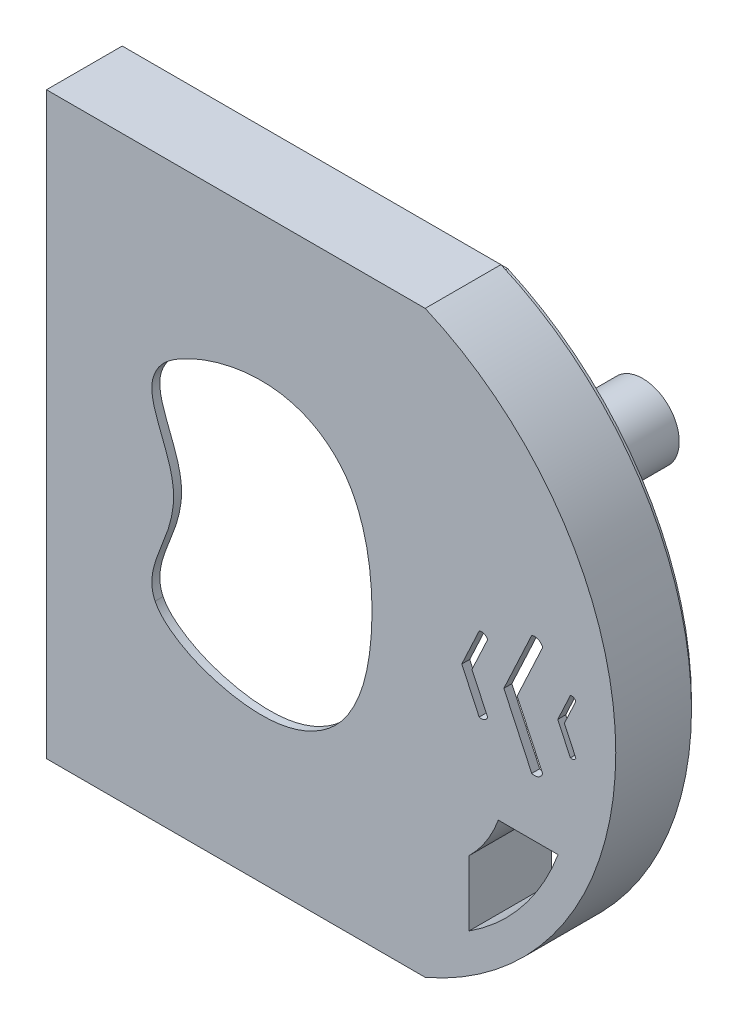
SolidWorks part; units mm, degrees
ref_plane "Front Plane" through (0, 0, 0) normal (0, 0, 1) x (1, 0, 0)
ref_plane "Top Plane" through (0, 0, 0) normal (0, 1, 0) x (1, 0, 0)
ref_plane "Right Plane" through (0, 0, 0) normal (1, 0, 0) x (0, 0, -1)
sketch "Sketch1" plane through (0, 0, 0) normal (0, 0, 1) x (1, 0, 0)
  line L1 (-74.2297, 45.7275) -> (-49.2297, 45.7275)
  line L2 (-74.2297, 45.7275) -> (-74.2297, 5.7275)
  line L3 (-74.2297, 5.7275) -> (-49.2297, 5.7275)
  line L4 (-49.2297, 45.7275) -> (-49.2297, 5.7275)
  dimension "D1" = 40
  dimension "D2" = 25
extrude "Boss-Extrude1" add sketch "Sketch1" along normal blind 0.5 and the other way blind 0.0001
sketch "Sketch2" plane through (0, 0, 0) normal (0, 0, 1) x (1, 0, 0)
  line L0 (-77.8888, 47.5275) -> (-77.8888, 3.9275)
  line L5 (-61.7297, 45.7275) -> (-61.7297, 25.7275)
  line L6 (-49.2297, 45.7275) -> (-74.2297, 45.7275) construction
  line L8 (-77.8888, 47.5275) -> (-49.3888, 47.5275)
  line L10 (-77.8888, 3.9275) -> (-49.3888, 3.9275)
  circle A1 centre (-42.3892, 25.7624) radius 48.5612
  arc A3 (-49.3888, 47.5275) -> (-49.3888, 3.9275) centre (-58.7867, 25.7275) cw
  dimension "D6" = 43.6
  dimension "D8" = 28.5
  dimension "D9" = 28.5
extrude "Boss-Extrude5" add sketch "Sketch2" along normal blind 6.1 and the other way blind 0.1 contours L8 L0 region at (-58.2685, 25.7275, 0)
sketch "Sketch8" plane through (0, 0, 0) normal (0, 0, 1) x (1, 0, 0)
  line L0 (-76.8888, 46.5275) -> (-76.8888, 4.9275)
  line L1 (-76.8888, 4.9275) -> (-49.3888, 4.9275)
  line L2 (-76.8888, 46.5275) -> (-49.3888, 46.5275)
  line L3 (-77.8888, 47.5275) -> (-77.8888, 3.9275) construction
  arc A0 (-49.3888, 4.9275) -> (-49.3888, 46.5275) centre (-58.9321, 25.7275) ccw
  arc A2 (-49.3888, 3.9275) -> (-49.3888, 47.5275) centre (-58.7867, 25.7275) ccw construction
  point P8 (-36.0473, 25.7275)
  point P12 (-35.0473, 25.7275)
  dimension "D1" = 1
  dimension "D2" = 1
  dimension "D3" = 1
  dimension "D4" = 1
extrude "Cut-Extrude2" cut sketch "Sketch8" against normal blind 4 and the other way blind 5.5 contours A0 L2 L0 L1
sketch "Sketch9" plane through (0, 0, 0) normal (0, 0, 1) x (1, 0, 0)
  line L0 (-37.7093, 30.2625) -> (-37.7093, 29.3916)
  line L1 (-37.7093, 22.0742) -> (-37.7093, 21.228)
  line L2 (-46.6022, 30.9745) -> (-46.6022, 30.0766)
  line L3 (-46.6022, 21.3784) -> (-46.6022, 20.6468)
  arc A3 (-37.7093, 30.2625) -> (-46.6022, 30.9745) centre (-42.5385, 25.8379) ccw
  arc A4 (-37.7093, 21.228) -> (-46.6022, 20.6468) centre (-42.4688, 25.7275) cw
  arc A5 (-37.7093, 29.3916) -> (-46.6022, 30.0766) centre (-42.4641, 25.732) ccw
  arc A6 (-37.7093, 22.0742) -> (-46.6022, 21.3784) centre (-42.4688, 25.7275) cw
sketch "Sketch11" plane through (0, 0, -0.1) normal (0, 0, -1) x (-1, 0, 0)
  line L0 (76.8888, 46.5275) -> (76.8888, 4.9275) construction
  line L1 (49.3888, 47.5275) -> (77.8888, 47.5275)
  line L2 (49.3888, 4.4275) -> (77.3888, 4.4275)
  line L3 (77.3888, 4.4275) -> (77.3888, 47.0275)
  line L4 (77.3888, 47.0275) -> (49.3888, 47.0275)
  line L5 (77.8888, 47.5275) -> (77.8888, 3.9275)
  line L6 (77.8888, 3.9275) -> (49.3888, 3.9275)
  arc A0 (49.3888, 47.0275) -> (49.3888, 4.4275) centre (58.8568, 25.7275) ccw
  arc A1 (49.3888, 47.5275) -> (49.3888, 3.9275) centre (58.7867, 25.7275) ccw construction
  arc A2 (49.3888, 47.5275) -> (49.3888, 3.9275) centre (58.7867, 25.7275) ccw
  point P16 (35.0473, 25.7275)
  point P17 (35.5473, 25.7275)
  dimension "D1" = 0.5
  dimension "D2" = 0.5
  dimension "D3" = 0.5
  dimension "D4" = 0.5
extrude "Cut-Extrude3" cut sketch "Sketch11" against normal blind 0.5
sketch "Sketch16" plane through (-77.8888, 0, 0) normal (-1, 0, 0) x (0, 0, 1)
  line L0 (3.4, 25.7275) -> (3.4, 28.7275)
  line L4 (3.4, 25.7275) -> (3.4, 22.7275)
  line L6 (-2.6, 25.7275) -> (3.4, 28.7275)
  line L8 (-2.6, 25.7275) -> (3.4, 22.7275)
extrude "Cut-Extrude4" cut sketch "Sketch16" against normal blind 0.4 contours L8 L4 L0 L6
sketch "Sketch21" plane through (0, 0, 0) normal (0, 0, 1) x (1, 0, 0)
  line L8 (-46.6022, 13.7463) -> (-46.6022, 7.8405)
  line L12 (-39.3888, 16.9275) -> (-43.8888, 16.9275)
  line L29 (-46.1022, 8.5905) -> (-46.1022, 13.4963)
  line L30 (-39.3888, 17.4104) -> (-38.8722, 17.4104)
  line L34 (-43.8888, 17.4104) -> (-44.4053, 17.4104)
  line L39 (-46.6022, 13.4963) -> (-46.6022, 13.7463)
  line L43 (-46.6022, 8.5905) -> (-46.6022, 7.8405)
  line L44 (-44.4053, 17.4104) -> (-38.8722, 17.4104)
  arc A0 (-43.8888, 16.9275) -> (-46.1022, 13.4963) centre (-52.5399, 20.0787) cw
  arc A1 (-39.3888, 16.9275) -> (-46.1022, 8.5905) centre (-55.3129, 22.8791) cw
  arc A5 (-44.4053, 17.4104) -> (-46.6022, 13.7463) centre (-53.185, 20.1837) cw
  arc A6 (-38.8722, 17.4104) -> (-46.6022, 7.8405) centre (-55.0658, 22.5839) cw
  dimension "D1" = 4.9057
  dimension "D4" = 0.559
  dimension "D7" = 5.9057
sketch "Sketch26" plane through (0, 0, 5.5) normal (0, 0, -1) x (-1, 0, 0)
  line L0 (49.3888, 46.5275) -> (49.3888, 37.5275)
  circle A0 centre (43.8888, 37.5275) radius 1.25
  circle A1 centre (43.8888, 37.5275) radius 2.75
  point P6 (40.8845, 39.6012)
  dimension "D1" = 2.5
  dimension "D2" = 5.5
extrude "Boss-Extrude10" add sketch "Sketch26" along normal blind 10.2672 contours A1 A0 | A1 | A0 region at (-41.2165, 37.5275, 5.5)
extrude "Cut-Extrude10" cut sketch "Sketch21" against normal blind 8.134 and the other way blind 12 contours L12 A0 L29 A1
sketch "Sketch31" plane through (0, 0, 0) normal (0, 0, 1) x (1, 0, 0)
  line L8 (-46.6022, 13.7463) -> (-46.6022, 7.8405)
  line L44 (-44.4053, 17.4104) -> (-38.8722, 17.4104)
  line L45 (-46.1022, 8.5905) -> (-46.1022, 13.4963)
  line L46 (-39.3888, 16.9275) -> (-43.8888, 16.9275)
  arc A5 (-44.4053, 17.4104) -> (-46.6022, 13.7463) centre (-53.185, 20.1837) cw
  arc A6 (-38.8722, 17.4104) -> (-46.6022, 7.8405) centre (-55.0658, 22.5839) cw
  arc A7 (-46.1022, 8.5905) -> (-39.3888, 16.9275) centre (-55.3129, 22.8791) ccw
  arc A8 (-43.8888, 16.9275) -> (-46.1022, 13.4963) centre (-52.5399, 20.0787) cw
  dimension "D7" = 5.9057
extrude "Boss-Extrude11" add sketch "Sketch31" along normal blind 6.099 and the other way blind 0.1
sketch "Sketch32" plane through (0, 0, 6.1) normal (0, 0, 1) x (1, 0, 0)
  line L0 (-49.3888, 47.5275) -> (-49.3888, 3.9275)
  line L12 (-64.7084, -25.1636) -> (-66.7039, -20.6501)
  line L14 (-64.7084, -25.1636) -> (-66.8882, -29.8381)
  line L25 (-41.371, 30.2264) -> (-43.4688, 25.7275)
  line L28 (-41.371, 21.2287) -> (-43.4688, 25.7275)
  line L32 (-45.3278, 28.5317) -> (-46.6354, 25.7275)
  line L33 (-46.6354, 25.7275) -> (-45.3278, 22.9234)
  line L35 (-39.4125, 25.7275) -> (-38.464, 23.6935)
  line L40 (-39.4125, 25.7275) -> (-38.464, 27.7616)
  line L44 (-44.6869, 28.2943) -> (-45.8695, 25.7583)
  line L45 (-45.8695, 25.7583) -> (-44.6869, 23.2222)
  line L46 (-38.0533, 27.57) -> (-38.9125, 25.7275)
  line L47 (-38.9125, 25.7275) -> (-38.0533, 23.885)
  line L48 (-40.5496, 21.6117) -> (-42.4688, 25.7275)
  line L49 (-42.4688, 25.7275) -> (-40.5496, 29.8433)
  arc A0 (-44.6869, 23.2222) -> (-45.3278, 22.9234) centre (-45.1568, 23.3933) cw
  arc A2 (-44.6869, 28.2943) -> (-45.3278, 28.5317) centre (-45.1341, 28.0707) ccw
  arc A4 (-38.0533, 23.885) -> (-38.464, 23.6935) centre (-38.3544, 23.9946) cw
  arc A5 (-40.5496, 21.6117) -> (-41.371, 21.2287) centre (-41.1518, 21.8309) cw
  arc A6 (-41.371, 30.2264) -> (-40.5496, 29.8433) centre (-41.1518, 29.6242) cw
  arc A7 (-38.0533, 27.57) -> (-38.464, 27.7616) centre (-38.3544, 27.4604) ccw
extrude "Cut-Extrude11" cut sketch "Sketch32" against normal blind 6.134 contours L40 L35 | L28 L25 | L33 L32 region at (-40.9212, 30.1186, 6.1) region at (-44.9813, 28.4832, 6.1) region at (-38.899, 26.7263, 6.1)
sketch "Sketch33" plane through (0, 0, 0) normal (0, 0, 1) x (1, 0, 0)
  line L0 (-35.0473, 25.7275) -> (-77.8888, 25.7275)
  line L1 (-77.8888, 47.5275) -> (-77.8888, 3.9275) construction
  arc A0 (-49.3888, 3.9275) -> (-49.3888, 47.5275) centre (-58.7867, 25.7275) ccw construction
  spline S0 degree 3 poles (-69.7155, 18.2832) (-70.0608, 19.0122) (-69.8938, 20.7821) (-68.885, 22.8038) (-68.4119, 24.5765) (-68.2539, 26.022) (-68.5483, 27.644) (-69.1844, 29.246) (-69.7845, 30.7924) (-70.1192, 32.2842) (-69.3838, 34.0683) (-67.3795, 35.3657) (-64.6417, 36.4038) (-61.448, 36.8282) (-58.0624, 36.164) (-55.4514, 34.1332) (-53.6917, 30.4586) (-53.4083, 27.6398) (-53.384, 25.7513) knots 0 0 0 0 0.056113 0.130583 0.168191 0.193562 0.239298 0.290151 0.322884 0.364734 0.400905 0.460049 0.537277 0.621513 0.698396 0.791261 0.857327 1 1 1 1
  spline S1 degree 3 poles (-53.384, 25.7513) (-53.4198, 23.7713) (-53.7116, 20.6353) (-55.8525, 16.8571) (-59.6416, 14.5638) (-64.3205, 14.8709) (-67.9897, 16.3754) (-69.4248, 17.6944) (-69.7155, 18.2832) knots 0 0 0 0 0.24488 0.378469 0.518271 0.765302 0.920676 1 1 1 1
extrude "Cut-Extrude15" cut sketch "Sketch33" against normal blind 1.134 and the other way blind 45 contours S0 S1
sketch "Sketch39" plane through (-77.8888, 0, 0) normal (-1, 0, 0) x (0, 0, 1)
  line L3 (4.25, 36.8775) -> (4.25, 35.8775)
  line L5 (4.25, 35.8775) -> (2.25, 35.8775)
  line L6 (4.25, 35.8775) -> (4.25, 37.8775)
  line L7 (4.25, 37.8775) -> (2.25, 37.8775)
  line L8 (2.25, 35.8775) -> (2.25, 37.8775)
extrude "Boss-Extrude13" add sketch "Sketch39" along normal blind 0.0001 and the other way blind 3 contours L8 L5 L3 L6 L7 region at (-77.8888, 36.8775, 3.25)
sketch "Sketch40" plane through (-77.8889, 0, 0) normal (-1, 0, 0) x (0, 0, 1)
  line L1 (2.25, 37.8775) -> (4.25, 37.8775)
  line L2 (2.25, 37.8775) -> (2.25, 35.8775)
  line L3 (2.25, 35.8775) -> (4.25, 35.8775)
  line L4 (4.25, 37.8775) -> (4.25, 35.8775)
extrude "Cut-Extrude17" cut sketch "Sketch40" against normal blind 0.25
sketch "Sketch41" plane through (-77.8888, 0, 0) normal (-1, 0, 0) x (0, 0, 1)
  point P4 (-1.5055, 39.5439)
sketch "Sketch43" plane through (-77.8888, 0, 0) normal (-1, 0, 0) x (0, 0, 1)
  circle A0 centre (3.25, 36.8775) radius 0.25
extrude "Cut-Extrude19" cut sketch "Sketch43" against normal blind 3.25 contours A0
sketch "Sketch45" plane through (0, 0, 2.25) normal (0, 0, -1) x (-1, 0, 0)
  line L5 (74.8888, 37.8775) -> (76.8888, 37.8775) construction
  line L6 (76.8888, 35.8775) -> (75.8888, 35.8775)
  line L7 (76.8888, 35.8775) -> (76.8888, 37.8775)
  line L8 (76.8888, 37.8775) -> (75.8888, 37.8775)
  line L9 (75.8888, 35.8775) -> (75.8888, 37.8775)
extrude "Boss-Extrude14" add sketch "Sketch45" along normal blind 6.25
sketch "Sketch51" plane through (0, 37.8775, 0) normal (0, 1, 0) x (1, 0, 0)
  line L0 (-75.8888, 4) -> (-76.8888, 2.05)
  line L1 (-76.8888, 4) -> (-76.8888, 0.1) construction
  line L2 (-76.8888, 2.05) -> (-75.4934, 2.05)
  line L3 (-75.4934, 2.05) -> (-75.8888, 4)
  line L4 (-76.8888, 2.05) -> (-76.8888, 4)
  line L5 (-76.8888, 4) -> (-75.8888, 4)
  line M3 (-75.8888, 4) -> (-76.8888, 4)
  line M4 (-76.8888, 4) -> (-76.8888, 0.1)
extrude "Cut-Extrude21" cut sketch "Sketch51" against normal blind 4.25 and the other way blind 2 contours L0 M3 M4 region at (-76.5554, 37.8775, -3.35)
sketch "Sketch52" plane through (0, 37.8775, 0) normal (0, 1, 0) x (1, 0, 0)
  line L0 (-75.6888, 2.05) -> (-75.4888, 2.05)
  line L1 (-75.8888, 4) -> (-75.4888, 2.05)
  line L3 (-75.8888, 4) -> (-75.8888, -2.25) construction
  line L4 (-75.8888, 3.025) -> (-75.6888, 2.05)
  line L11 (-75.8888, 4) -> (-76.8888, 2.05)
  line L12 (-76.8888, 2.05) -> (-76.8888, 0.1)
  line L13 (-76.8888, 0.1) -> (-76.8888, -4.25)
  line L14 (-76.8888, -4.25) -> (-74.8888, -4.25)
  line L15 (-74.8888, -4.25) -> (-74.8888, -2.25)
  line L16 (-74.8888, -2.25) -> (-75.8888, -2.25)
  line L17 (-75.8888, -2.25) -> (-75.8888, 4)
  line L18 (-75.8888, 4) -> (-76.8888, 2.05)
  line L19 (-76.8888, 2.05) -> (-76.8888, 0.1)
  line L20 (-76.8888, 0.1) -> (-76.8888, -4.25)
  line L21 (-76.8888, -4.25) -> (-74.8888, -4.25)
  line L22 (-74.8888, -4.25) -> (-74.8888, -2.25)
  line L23 (-74.8888, -2.25) -> (-75.8888, -2.25)
  line L24 (-75.8888, -2.25) -> (-75.8888, 3.025)
  dimension "D1" = 0
extrude "Boss-Extrude15" add sketch "Sketch52" along normal blind 1.25 and the other way blind 3.25
sketch "Sketch53" plane through (0, 39.1275, 0) normal (0, 1, 0) x (1, 0, 0)
  line L0 (-76.8888, 2.05) -> (-76.8888, 0.1)
  point P4 (-500000, 1.3492)
